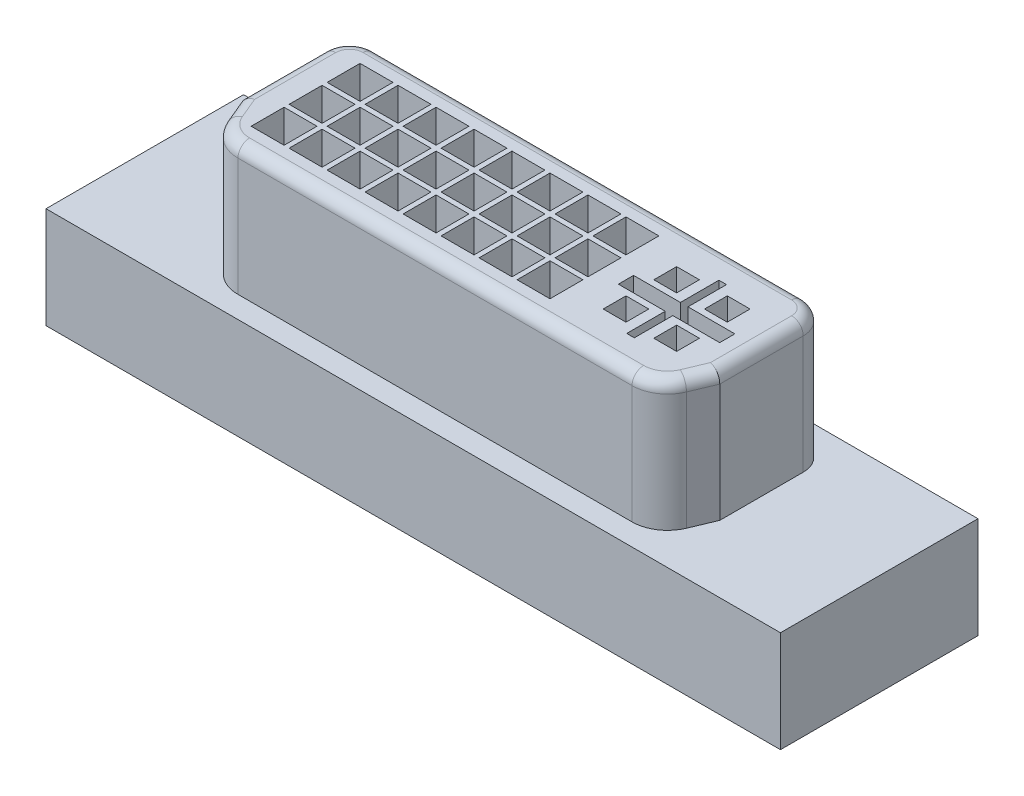
SolidWorks part; units mm, degrees
ref_plane "Front Plane" through (0, 0, 0) normal (0, 0, 1) x (1, 0, 0)
ref_plane "Top Plane" through (0, 0, 0) normal (0, 1, 0) x (1, 0, 0)
ref_plane "Right Plane" through (0, 0, 0) normal (1, 0, 0) x (0, 0, -1)
sketch "Sketch1" plane through (0, 0, 0) normal (0, 1, 0) x (1, 0, 0)
  line L0 (-18.415, 0) -> (18.415, 0) construction
  line L1 (-18.415, 4.953) -> (18.415, 4.953)
  line L2 (-18.415, 4.953) -> (-18.415, -4.953)
  line L3 (-18.415, -4.953) -> (18.415, -4.953)
  line L4 (18.415, 4.953) -> (18.415, -4.953)
  line L5 (-18.415, 4.953) -> (18.415, -4.953) construction
  line L6 (-18.415, -4.953) -> (18.415, 4.953) construction
  line L7 (0, 4.953) -> (0, -4.953) construction
  circle A0 centre (-16.256, 0) radius 1.2188 construction
  circle A1 centre (16.256, 0) radius 1.2188 construction
  point P0 (0, 0)
  dimension "D1" = 36.83
  dimension "D2" = 9.906
  dimension "D3" = 32.512
extrude "Boss-Extrude1" add sketch "Sketch1" against normal blind 5.08
sketch "Sketch2" plane through (0, 0, 0) normal (0, 1, 0) x (1, 0, 0)
  line L0 (-9.525, 0) -> (3.81, 0) construction
  line L1 (-10.7442, 3.8608) -> (10.7442, 3.8608)
  line L2 (-12.0142, 2.5908) -> (-12.0142, -1.5948)
  line L3 (-9.8806, -3.8608) -> (9.8806, -3.8608)
  line L4 (12.0142, 2.5908) -> (12.0142, -1.5948)
  line L5 (-12.0142, 3.8608) -> (12.0142, -3.8608) construction
  line L6 (-12.0142, -3.8608) -> (12.0142, 3.8608) construction
  line L7 (-9.525, 1.905) -> (9.525, 1.905) construction
  line L8 (0, 1.905) -> (0, 0) construction
  line L9 (-9.525, 1.905) -> (-9.525, 0) construction
  line L10 (3.81, 0) -> (12.7, 0) construction
  line L11 (10.0965, -0.6985) -> (10.0965, -1.8415)
  line L12 (6.985, -1.27) -> (9.525, -1.27) construction
  line L13 (6.985, -1.27) -> (6.985, 1.27) construction
  line L14 (6.985, 1.27) -> (9.525, 1.27) construction
  line L15 (9.525, -1.27) -> (9.525, 1.27) construction
  line L16 (6.985, -1.27) -> (9.525, 1.27) construction
  line L17 (6.985, 1.27) -> (9.525, -1.27) construction
  line L18 (8.9535, 1.8415) -> (10.0965, 1.8415)
  line L19 (8.9535, 1.8415) -> (8.9535, 0.6985)
  line L20 (8.9535, 0.6985) -> (10.0965, 0.6985)
  line L21 (10.0965, 1.8415) -> (10.0965, 0.6985)
  line L22 (8.9535, 1.8415) -> (10.0965, 0.6985) construction
  line L23 (8.9535, 0.6985) -> (10.0965, 1.8415) construction
  line L24 (8.9535, -0.6985) -> (10.0965, -0.6985)
  line L25 (8.9535, -0.6985) -> (9.525, -1.27) construction
  line L26 (8.9535, -0.6985) -> (8.9535, -1.8415)
  line L27 (8.9535, -1.8415) -> (10.0965, -0.6985) construction
  line L28 (8.9535, -1.8415) -> (10.0965, -1.8415)
  line L29 (7.5565, -0.6985) -> (7.5565, -1.8415)
  line L30 (6.4135, -0.6985) -> (7.5565, -0.6985)
  line L31 (6.4135, -0.6985) -> (7.5565, -1.8415) construction
  line L32 (6.4135, -0.6985) -> (6.4135, -1.8415)
  line L33 (6.985, -1.27) -> (7.5565, -0.6985) construction
  line L34 (6.4135, -1.8415) -> (7.5565, -1.8415)
  line L35 (7.5565, 1.8415) -> (7.5565, 0.6985)
  line L36 (6.4135, 1.8415) -> (7.5565, 1.8415)
  line L37 (7.6075, 1.27) -> (7.5565, 0.6985) construction
  line L38 (6.4135, 1.8415) -> (6.4135, 0.6985)
  line L39 (6.4135, 0.6985) -> (7.5565, 1.8415) construction
  line L40 (6.4135, 0.6985) -> (7.5565, 0.6985)
  line L41 (9.525, -1.27) -> (10.0965, -1.8415) construction
  line L42 (-9.8806, -2.0828) -> (-11.5198, -2.7715) construction
  line L43 (-10.3505, 2.7305) -> (-8.6995, 2.7305)
  line L44 (-10.3505, 2.7305) -> (-10.3505, 1.0795)
  line L45 (-10.3505, 1.0795) -> (-8.6995, 1.0795)
  line L46 (-8.6995, 2.7305) -> (-8.6995, 1.0795)
  line L47 (-10.3505, 2.7305) -> (-8.6995, 1.0795) construction
  line L48 (-10.3505, 1.0795) -> (-8.6995, 2.7305) construction
  line L49 (-9.8806, -2.0828) -> (-9.8806, -3.8608) construction
  line L50 (-11.5198, -2.7715) -> (-12.0142, -1.5948)
  line L51 (11.5198, -2.7715) -> (12.0142, -1.5948)
  line L53 (5.715, 0.381) -> (10.795, 0.381)
  line L54 (5.715, 0.381) -> (5.715, -0.381)
  line L55 (5.715, -0.381) -> (10.795, -0.381)
  line L56 (10.795, 0.381) -> (10.795, -0.381)
  line L57 (5.715, 0.381) -> (10.795, -0.381) construction
  line L58 (5.715, -0.381) -> (10.795, 0.381) construction
  line L59 (8.0645, 2.3114) -> (8.4455, 2.3114)
  line L60 (8.0645, 2.3114) -> (8.0645, -2.3114)
  line L61 (8.0645, -2.3114) -> (8.4455, -2.3114)
  line L62 (8.4455, 2.3114) -> (8.4455, -2.3114)
  line L63 (8.0645, 2.3114) -> (8.4455, -2.3114) construction
  line L64 (8.0645, -2.3114) -> (8.4455, 2.3114) construction
  arc A0 (10.7442, 3.8608) -> (12.0142, 2.5908) centre (10.7442, 2.5908) cw
  arc A1 (-10.7442, 3.8608) -> (-12.0142, 2.5908) centre (-10.7442, 2.5908) ccw
  arc A2 (-11.5198, -2.7715) -> (-9.8806, -3.8608) centre (-9.8806, -2.0828) ccw
  arc A3 (11.5198, -2.7715) -> (9.8806, -3.8608) centre (9.8806, -2.0828) cw
  point P0 (0, 0)
  point P12 (8.255, 0)
  point P54 (8.255, 0)
  point P59 (8.255, 0)
  dimension "D9" = 1.27
  dimension "D11" = 3.556
  dimension "D1" = 24.0284
  dimension "D2" = 7.7216
  dimension "D3" = 13.335
  dimension "D4" = 19.05
  dimension "D5" = 1.905
  dimension "D6" = 2.54
  dimension "D7" = 1.143
  dimension "D8" = 1.651
  dimension "D10" = 2.1336
  dimension "D12" = 67.21
  dimension "D13" = 5.08
  dimension "D14" = 0.762
  dimension "D15" = 4.6228
  dimension "D16" = 0.381
extrude "Boss-Extrude2" add sketch "Sketch2" along normal blind 6.5024 contours L3 A3 L51 L4 A0 L1 A1 L2 L50 A2
fillet "Fillet1" radius 0.5842 10 edges at (-11.767, 6.5024, 2.1832) (-12.0142, 6.5024, -0.498) (-11.6422, 6.5024, -3.4888) (0, 6.5024, -3.8608) (11.6422, 6.5024, -3.4888) (12.0142, 6.5024, -0.498) (11.767, 6.5024, 2.1832) (10.8647, 6.5024, 3.5636) (0, 6.5024, 3.8608) (-10.8647, 6.5024, 3.5636)
sketch "Sketch3" plane through (0, 6.5024, 0) normal (0, 1, 0) x (1, 0, 0)
  line L6 (-11.43, 2.5908) -> (-11.43, -1.4771)
  line L7 (-11.43, -1.4771) -> (-10.9812, -2.5452)
  line L8 (-9.8806, -3.2766) -> (9.8806, -3.2766)
  line L9 (10.9812, -2.5452) -> (11.43, -1.4771)
  line L10 (11.43, -1.4771) -> (11.43, 2.5908)
  line L11 (10.7442, 3.2766) -> (-10.7442, 3.2766)
  line L12 (-11.43, 2.5908) -> (-11.43, -1.4771)
  line L13 (-11.43, -1.4771) -> (-10.9812, -2.5452)
  line L14 (-9.8806, -3.2766) -> (9.8806, -3.2766)
  line L15 (10.9812, -2.5452) -> (11.43, -1.4771)
  line L16 (11.43, -1.4771) -> (11.43, 2.5908)
  line L17 (10.7442, 3.2766) -> (-10.7442, 3.2766)
  arc A4 (-10.9812, -2.5452) -> (-9.8806, -3.2766) centre (-9.8806, -2.0828) ccw
  arc A5 (9.8806, -3.2766) -> (10.9812, -2.5452) centre (9.8806, -2.0828) ccw
  arc A6 (11.43, 2.5908) -> (10.7442, 3.2766) centre (10.7442, 2.5908) ccw
  arc A7 (-10.7442, 3.2766) -> (-11.43, 2.5908) centre (-10.7442, 2.5908) ccw
  arc A8 (-10.9812, -2.5452) -> (-9.8806, -3.2766) centre (-9.8806, -2.0828) ccw
  arc A9 (9.8806, -3.2766) -> (10.9812, -2.5452) centre (9.8806, -2.0828) ccw
  arc A10 (11.43, 2.5908) -> (10.7442, 3.2766) centre (10.7442, 2.5908) ccw
  arc A11 (-10.7442, 3.2766) -> (-11.43, 2.5908) centre (-10.7442, 2.5908) ccw
  dimension "D1" = 0
extrude "Cut-Extrude2" cut sketch "Sketch3" against normal blind 11.5316
extrude "Boss-Extrude3" add sketch "Sketch3<2>" against normal blind 11.5316 separate body
sketch "Sketch3<2>" plane through (0, 6.5024, 0) normal (0, 1, 0) x (1, 0, 0) same geometry as "Sketch3"
extrude "Cut-Extrude1" cut sketch "Sketch2<3>" against normal blind 11.5316 from surface contours L46 L45 L44 L43 starting at face at (0, 6.5024, 0.2911)
sketch "Sketch2<3>" plane through (0, 0, 0) normal (0, 1, 0) x (1, 0, 0) same geometry as "Sketch2"
pattern_linear "LPattern1" count 8 spacing 1.905 along (1, 0, 0) count 3 spacing 1.905 along (0, 0, 1) of "Cut-Extrude1"
extrude "Cut-Extrude3" cut sketch "Sketch2<4>" against normal blind 11.5316 from surface contours L28 L11 L24 L26 | L34 L29 L30 L32 | L61 L62 L59 L60 | L55 L56 L53 L54 | L21 L20 L19 L18 | L35 L40 L38 L36 starting at face at (0, 6.5024, 0.2911)
sketch "Sketch2<4>" plane through (0, 0, 0) normal (0, 1, 0) x (1, 0, 0) same geometry as "Sketch2"
